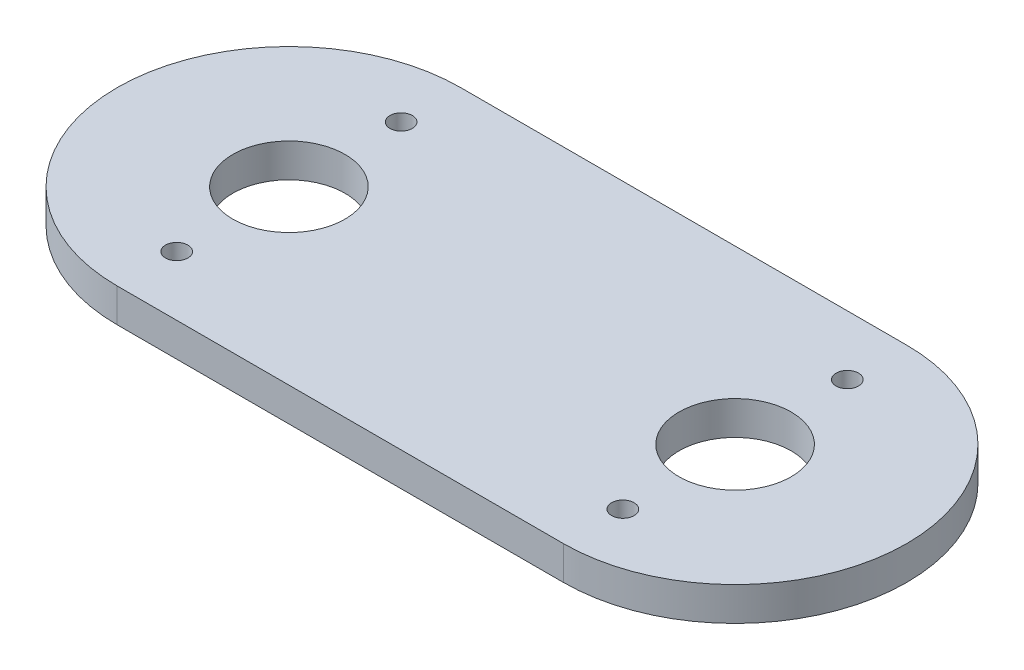
SolidWorks part; units mm, degrees
ref_plane "Front Plane" through (0, 0, 0) normal (0, 0, 1) x (1, 0, 0)
ref_plane "Top Plane" through (0, 0, 0) normal (0, 1, 0) x (1, 0, 0)
ref_plane "Right Plane" through (0, 0, 0) normal (1, 0, 0) x (0, 0, -1)
sketch "Sketch1" plane through (0, 0, 0) normal (0, 1, 0) x (1, 0, 0)
  line L0 (-31.9723, 0) -> (7.786, 0)
  line L1 (7.786, -30.6106) -> (-31.9723, -30.6106)
  arc A0 (7.786, 0) -> (7.786, -30.6106) centre (7.786, -15.3053) cw
  arc A1 (-31.9723, -30.6106) -> (-31.9723, 0) centre (-31.9723, -15.3053) cw
  dimension "D1" = 39.7583
  dimension "D2" = 30.6106
extrude "Boss-Extrude1" add sketch "Sketch1" along normal blind 3
sketch "Sketch2" plane through (0, 3, 0) normal (0, 1, 0) x (1, 0, 0)
  line L0 (-12.0932, -54.7734) -> (-12.0932, 0) construction
  line L1 (-31.9723, 0) -> (-31.9723, -30.6106) construction
  line L2 (-54.6054, -15.3053) -> (-12.0932, -15.3053) construction
  line L3 (7.786, 0) -> (-31.9723, 0) construction
  circle A0 centre (-31.9723, -15.3053) radius 5
  circle A1 centre (-31.9723, -5.3053) radius 1
  circle A2 centre (-31.9723, -25.3053) radius 1
  circle A3 centre (7.786, -5.3053) radius 1
  circle A4 centre (7.786, -15.3053) radius 5
  circle A5 centre (7.786, -25.3053) radius 1
  point P23 (-12.0932, 0)
  dimension "D1" = 10
  dimension "D2" = 2
  dimension "D3" = 10
extrude "Cut-Extrude1" cut sketch "Sketch2" against normal through all
